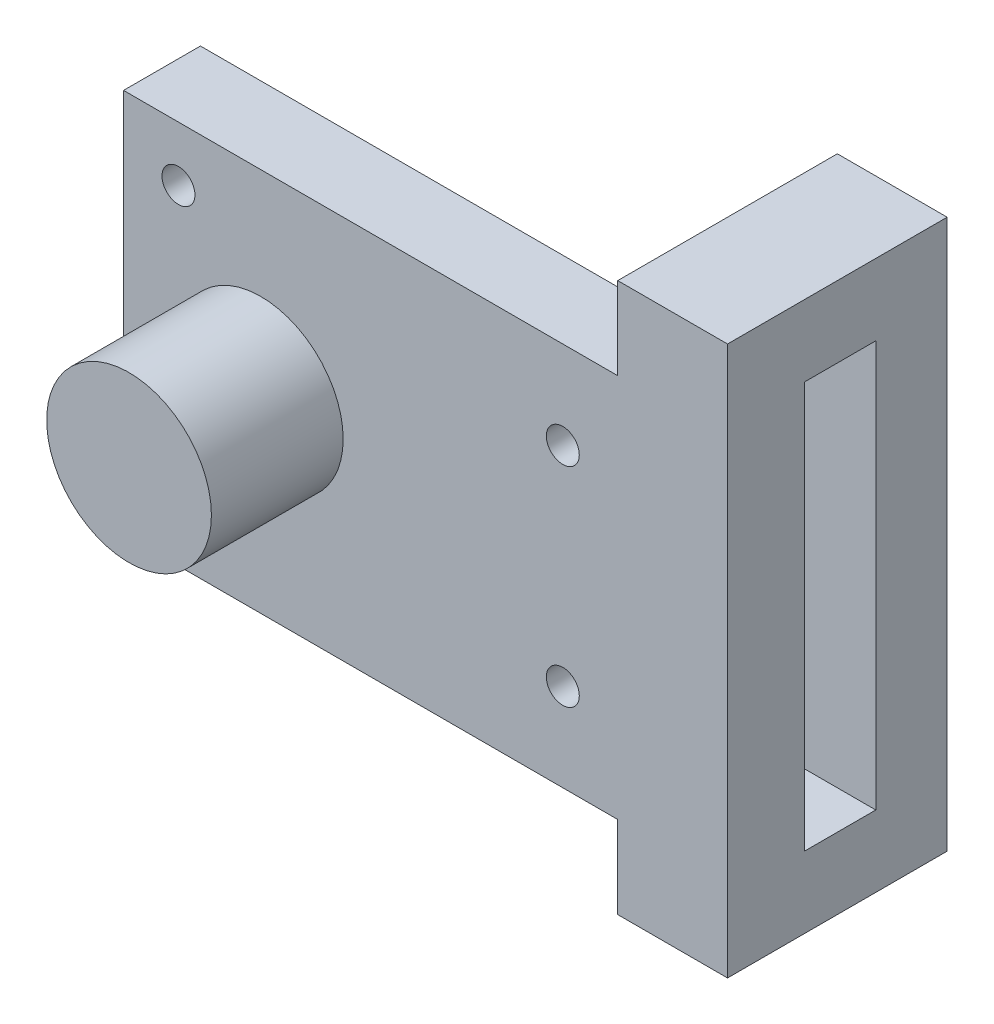
SolidWorks part; units mm, degrees
ref_plane "Front Plane" through (0, 0, 0) normal (0, 0, 1) x (1, 0, 0)
ref_plane "Top Plane" through (0, 0, 0) normal (0, 1, 0) x (1, 0, 0)
ref_plane "Right Plane" through (0, 0, 0) normal (1, 0, 0) x (0, 0, -1)
sketch "Sketch1" plane through (0, 0, 0) normal (0, 0, 1) x (1, 0, 0)
  line L1 (-92.5, 17.5) -> (-47.5, 17.5)
  line L2 (-92.5, 17.5) -> (-92.5, -17.5)
  line L3 (-92.5, -17.5) -> (-47.5, -17.5)
  line L4 (-47.5, 17.5) -> (-47.5, -17.5)
  line L5 (-92.5, 0) -> (-56.7435, 0) construction
  circle A0 centre (-87.5, 12.5) radius 1.5
  circle A1 centre (-87.5, -12.5) radius 1.5
  circle A2 centre (-52.5, 9.5) radius 1.5
  circle A3 centre (-52.5, -9.5) radius 1.5
  circle A4 centre (-80, 0) radius 4.25
  dimension "D2" = 3
  dimension "D5" = 8.5
  dimension "D1" = 45
  dimension "D3" = 5
  dimension "D4" = 5
extrude "Boss-Extrude1" add sketch "Sketch1" along normal blind 7 contours L4 L1 L2 A4 L3 A3 A2 A0 A1 | L5 A4 | A4 L5 region at (-80, 1.8038, 0) region at (-80, -1.8038, 0) region at (-70, 16.9299, 0)
sketch "Sketch2" plane through (-47.5, 0, 0) normal (1, 0, 0) x (0, 0, -1)
  line L1 (0, 25) -> (-7, 25)
  line L2 (0, 25) -> (0, -25)
  line L3 (0, -25) -> (-7, -25)
  line L4 (-7, 25) -> (-7, -25)
  line L6 (-7, 17.5) -> (0, 17.5) construction
  line L7 (-7, -17.5) -> (0, -17.5) construction
  line L8 (-7, 17.5) -> (-7, -17.5) construction
  point P6 (-20, -17.5)
  point P7 (0, 0)
  point P8 (-20, -17.5)
  point P9 (0, 0)
  point P10 (-13.6549, -17.5)
  point P11 (-10, -24.2657)
  point P12 (-10, 23.9139)
  point P15 (0, 0)
  point P16 (0, 0)
  dimension "D2" = 7.5
  dimension "D3" = 7.5
extrude "Boss-Extrude2" add sketch "Sketch2" along normal blind 10
sketch "Sketch3" plane through (0, 0, 0) normal (0, 0, -1) x (-1, 0, 0)
  line L0 (37.5, -25) -> (37.5, 25) construction
  line L1 (47.5, 25) -> (37.5, 25)
  line L2 (47.5, 25) -> (47.5, 18.5)
  line L3 (47.5, 18.5) -> (37.5, 18.5)
  line L4 (37.5, 25) -> (37.5, 18.5)
  line L5 (92.5, 17.5) -> (47.5, 17.5) construction
  line L6 (13.2, 0) -> (-13.2, 0) construction
  line L7 (47.5, -18.5) -> (37.5, -18.5)
  line L8 (37.5, -25) -> (37.5, -18.5)
  line L9 (47.5, -25) -> (37.5, -25)
  line L10 (47.5, -25) -> (47.5, -18.5)
  dimension "D1" = 1
extrude "Boss-Extrude3" add sketch "Sketch3" along normal blind 6.5
sketch "Sketch4" plane through (0, 0, -6.5) normal (0, 0, -1) x (-1, 0, 0)
  line L1 (47.5, 25) -> (37.5, 25)
  line L2 (47.5, 25) -> (47.5, -25)
  line L3 (47.5, -25) -> (37.5, -25)
  line L4 (37.5, 25) -> (37.5, -25)
extrude "Boss-Extrude4" add sketch "Sketch4" along normal blind 6.5
sketch "Sketch5" plane through (0, 0, 7) normal (0, 0, 1) x (1, 0, 0)
  circle A0 centre (-80, 0) radius 7.5
  dimension "D1" = 15
extrude "Boss-Extrude5" add sketch "Sketch5" along normal blind 12
extrude "Cut-Extrude1" cut sketch "Sketch1<3>" along normal blind 16 contours L5 A4 | A4 L5 region at (-80, 1.8038, 0) region at (-80, -1.8038, 0)
sketch "Sketch1<3>" plane through (0, 0, 0) normal (0, 0, 1) x (1, 0, 0) same geometry as "Sketch1"
